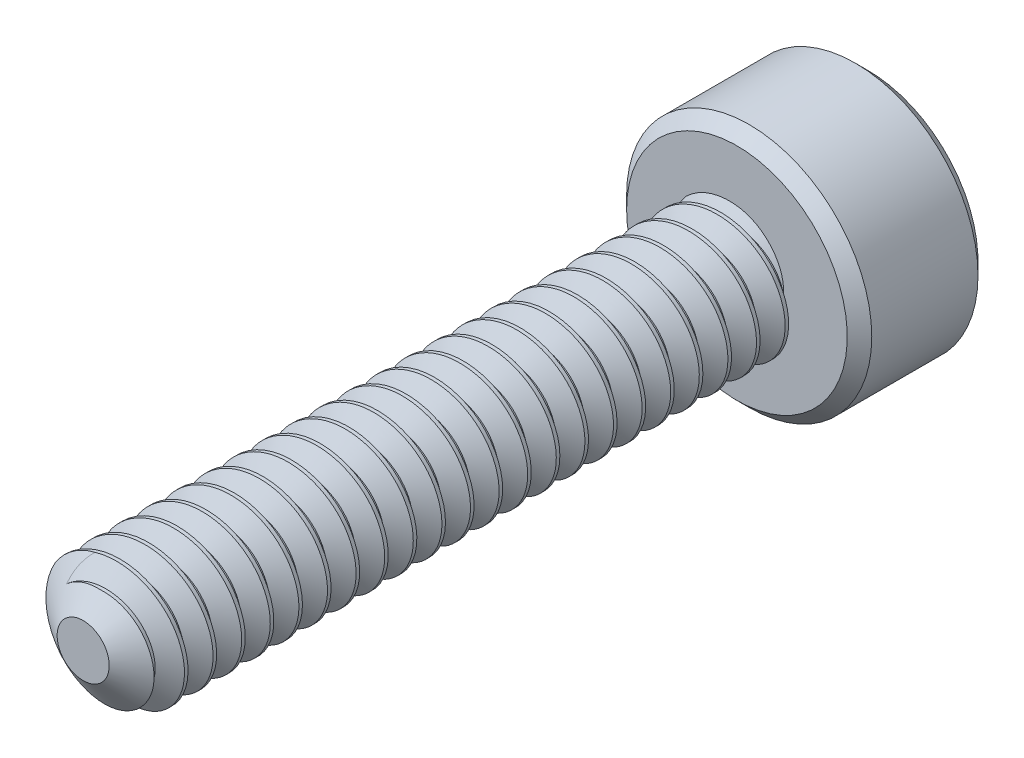
SolidWorks part; units mm, degrees
note: '?' marks a value the reader was unsure of.
ref_plane "Front Plane" through (0, 0, 0) normal (0, 0, 1) x (1, 0, 0)
ref_plane "Top Plane" through (0, 0, 0) normal (0, 1, 0) x (1, 0, 0)
ref_plane "Right Plane" through (0, 0, 0) normal (1, 0, 0) x (0, 0, -1)
sketch "Sketch1" plane through (0, 0, 0) normal (0, 0, 1) x (1, 0, 0)
  circle A0 centre (0, 0) radius 0.8
  dimension "OD" = 1.6
extrude "Extrude1" add sketch "Sketch1" against normal blind 8
sketch "Sketch2" plane through (0, 0, 0) normal (0, 0, 1) x (1, 0, 0)
  circle A0 centre (0, 0) radius 0.8 construction
  circle A1 centre (0, 0) radius 0.8
curve "Helix/Spiral1" pitch 0.35 height 8.35 radius 0.8 centre (0, 0, 0) axis (0, 0, -1) start towards (0, 1, 0) parameters "pitch"=0.35
sketch "Sketch3" plane through (0, 0, 0) normal (1, 0, 0) x (0, 0, -1)
  line L0 (-0.3063, 0.8) -> (-0.175, 0.5727)
  line L1 (-0.175, 0.5727) -> (-0.1313, 0.5727)
  line L2 (-0.1313, 0.5727) -> (0, 0.8)
  line L3 (-0.3063, 0.8) -> (0, 0.8)
  line L4 (-0.1531, 0.8) -> (-0.1531, 0.5727) construction
  line L5 (-0.2406, 0.6863) -> (-0.0656, 0.6863) construction
  line L6 (0, 0.8) -> (0, -0.8) construction
  dimension "D1" = 0.0437
  dimension "D2" = 0.175
  dimension "D3" = 60
sweep "Cut-Sweep1" cut profiles "Sketch3" path "Helix/Spiral1" align with end faces yes
sketch "Sketch4" plane through (0, 0, 0) normal (1, 0, 0) x (0, 0, -1)
  line L0 (0.337, 0.8) -> (0, 0.3187)
  line L1 (0, 0.3187) -> (0, 0.8)
  line L2 (0.337, 0.8) -> (0, 0.8)
  line L3 (-0.3063, 0.8) -> (0, 0.8) construction
  line L4 (0, 0) -> (7.0209, 0) construction
  dimension "D1" = 55
  dimension "D2" = 0.254
revolve "Cut-Revolve1" cut sketch "Sketch4" angle 360 about L4
sketch "Sketch6" plane through (0, 0, -8) normal (0, 0, -1) x (-1, 0, 0)
  circle A0 centre (0, 0) radius 1.5
  dimension "head dia" = 3
extrude "Extrude2" add sketch "Sketch6" along normal blind 1.6
sketch "Sketch7" plane through (0, 0, -9.6) normal (0, 0, -1) x (-1, 0, 0)
  line L1 (0, 0.866) -> (-0.75, 0.433)
  line L2 (-0.75, 0.433) -> (-0.75, -0.433)
  line L3 (-0.75, -0.433) -> (0, -0.866)
  line L4 (0, -0.866) -> (0.75, -0.433)
  line L5 (0.75, -0.433) -> (0.75, 0.433)
  line L6 (0.75, 0.433) -> (0, 0.866)
  circle A0 centre (0, 0) radius 0.75 construction
  dimension "hex dia" = 1.5
extrude "Cut-Extrude1" cut sketch "Sketch7" against normal blind 1.125
sketch "Sketch8" plane through (0, 0, -9.6) normal (0, 0, -1) x (-1, 0, 0)
  circle A0 centre (0, 0) radius 0.866
extrude "Cut-Extrude2" cut sketch "Sketch8" against normal through all draft 45
chamfer "Chamfer1" distance 0.15 angle 45 2 edges at (-1.5, 0, -9.6) (-1.5, 0, -8)
sketch "Sketch10" plane through (0, 0, -8) normal (0, 0, 1) x (1, 0, 0)
  circle A1 centre (0, 0) radius 0.8
  circle A2 centre (0, 0) radius 0.8
  dimension "D1" = 0
ref_plane "Plane1" through (0, 0, 0) normal (0, 0, 1) x (1, 0, 0)
extrude "partial thread" [suppressed] add sketch "Sketch10" along normal up to surface (36 mm away) separate body
chamfer "Chamfer2" [suppressed] distance 0.032 angle 45
combine bodies "Combine1" [suppressed] operation type? add bodies to combine 107 108
sketch "Sketch9" plane through (0, 0, 0) normal (1, 0, 0) x (0, 0, -1)
  line L0 (0, 0.8) -> (0, -0.8) construction
  line L1 (0.875, 0.8) -> (0.875, -0.8) construction
  dimension "D1" = 0.875
equation "\"D3@Helix/Spiral1\" = \"screw length@Extrude1\"+\"pitch@Helix/Spiral1\""
equation "\"D1@Sketch3\" = \"pitch@Helix/Spiral1\"*.125"
equation "\"D2@Sketch3\" = \"pitch@Helix/Spiral1\"*.5"
equation "\"D1@Cut-Extrude1\" = \"hex dia@Sketch7\"*.75"
equation "\"D1@Chamfer1\" = \"head dia@Sketch6\"*.05"
equation "\"D1@Sketch9\" = \"pitch@Helix/Spiral1\"*2.5"
equation "\"D1@Chamfer2\"=\"OD@Sketch1\"*.02"
